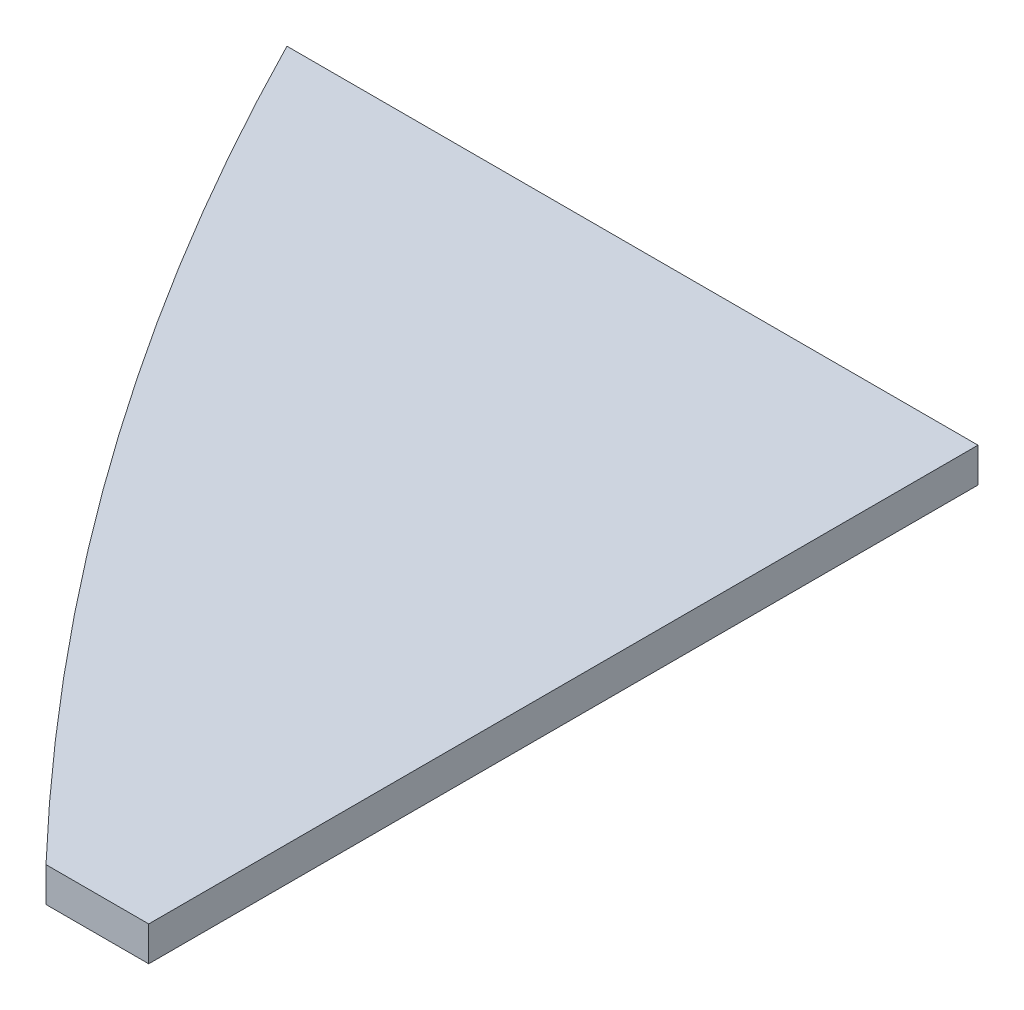
SolidWorks part; units mm, degrees
ref_plane "Front Plane" through (0, 0, 0) normal (0, 0, 1) x (1, 0, 0)
ref_plane "Top Plane" through (0, 0, 0) normal (0, 1, 0) x (1, 0, 0)
ref_plane "Right Plane" through (0, 0, 0) normal (1, 0, 0) x (0, 0, -1)
sketch "Sketch1" plane through (0, 0, 0) normal (0, 1, 0) x (1, 0, 0)
  line L0 (36.7862, 0) -> (-26.7138, 0)
  line L1 (36.7862, 0) -> (36.7862, -76.2)
  line L2 (27.3468, -76.2) -> (36.7862, -76.2)
  spline S0 degree 2 poles (-26.7138, 0) (-5.274, -42.1228) (27.3468, -76.2) knots 0 0 0 1 1 1
  dimension "D1" = 63.5
  dimension "D2" = 76.2
extrude "Boss-Extrude1" add sketch "Sketch1" against normal blind 3.175
